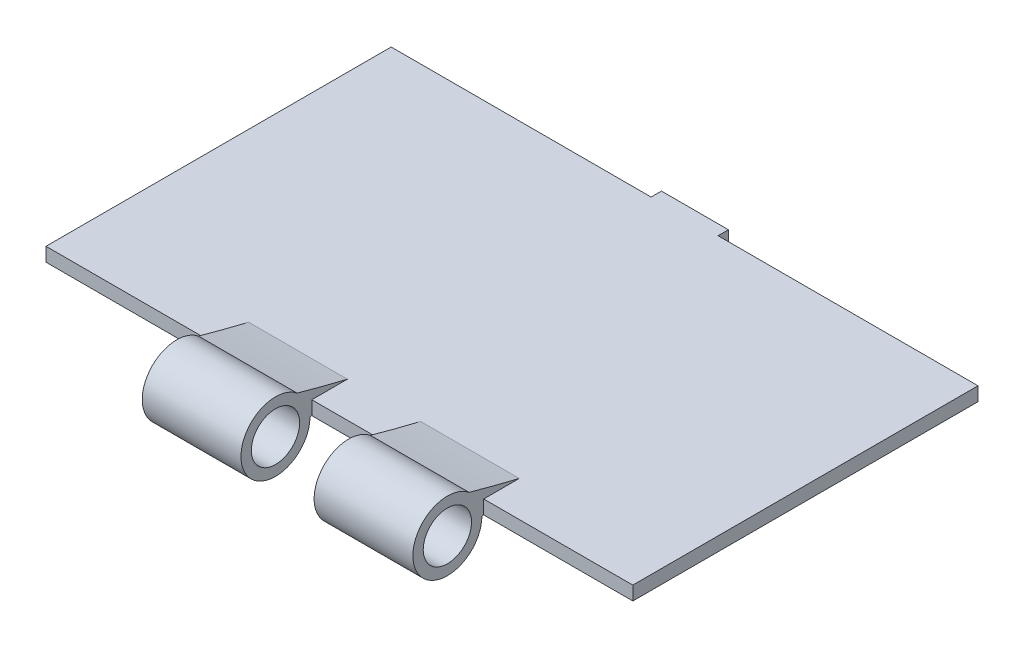
SolidWorks part; units mm, degrees
ref_plane "Plan de face" through (0, 0, 0) normal (0, 0, 1) x (1, 0, 0)
ref_plane "Plan de dessus" through (0, 0, 0) normal (0, 1, 0) x (1, 0, 0)
ref_plane "Plan de droite" through (0, 0, 0) normal (1, 0, 0) x (0, 0, -1)
sketch "Esquisse1" plane through (0, 0, 0) normal (0, 1, 0) x (1, 0, 0)
  line L1 (-42.5, 25) -> (42.5, 25)
  line L2 (-42.5, 25) -> (-42.5, -25)
  line L3 (-42.5, -25) -> (42.5, -25)
  line L4 (42.5, 25) -> (42.5, -25)
  line L5 (-42.5, 25) -> (42.5, -25) construction
  line L6 (-42.5, -25) -> (42.5, 25) construction
  point P0 (0, 0)
  dimension "D1" = 85
  dimension "D2" = 50
extrude "Boss.-Extru.1" add sketch "Esquisse1" along normal blind 2
ref_plane "Plan1" through (-18.3, 0, 0) normal (-1, 0, 0) x (0, 0, 1)
sketch "Esquisse2" plane through (-18.3, 0, 0) normal (-1, 0, 0) x (0, 0, 1)
  line L0 (25, 2) -> (25, 0) construction
  line L1 (-25, 2) -> (25, 2) construction
  line L2 (19.8455, 2) -> (25.3553, -0.0963)
  line L3 (-25, 0) -> (25, 0) construction
  circle A0 centre (30.26, 0) radius 5
  spline S0 degree 2 poles (27.1249, 3.895) (23.5046, 2.8738) (19.8455, 2) knots 0 0 0 1 1 1
  dimension "D1" = 10
  dimension "D2" = 5.26
  dimension "D3" = 0
extrude "Boss.-Extru.2" add sketch "Esquisse2" against normal blind 14.3 contours A0 S0 | A0 S0 L2 region at (-18.3, 1.9197, 23.8256) region at (-18.3, 0, 30.26)
sketch "Esquisse3" plane through (-18.3, 0, 0) normal (-1, 0, 0) x (0, 0, 1)
  circle A0 centre (30.26, 0) radius 3.5
  circle A1 centre (30.26, 0) radius 5 construction
  dimension "D1" = 0
  dimension "D2" = 7
extrude "Enlèv. mat.-Extru.1" cut sketch "Esquisse3" against normal up to surface (14.3 mm away) up to face at (-4, 0.9543, 26.8921)
pattern_linear "Répétition linéaire2" count 2 spacing 24.9 along (1, 0, 0) of "Enlèv. mat.-Extru.1", "Boss.-Extru.2"
ref_plane "Plan2" through (0, 0, 0) normal (1, 0, 0) x (0, 0, -1)
sketch "Esquisse4" plane through (0, 0, 0) normal (1, 0, 0) x (0, 0, -1)
  line L1 (25, 2) -> (26.5, 2)
  line L2 (25, 2) -> (25, -8)
  line L3 (25, -8) -> (26.5, -8)
  line L4 (26.5, 2) -> (26.5, -8)
  arc A0 (25, -8) -> (25, -6.5) centre (25, -7.25) cw
  dimension "D4" = 0.75
  dimension "D1" = 1.5
  dimension "D2" = 10
  dimension "D3" = 1.5
extrude "Boss.-Extru.3" add sketch "Esquisse4" along normal blind 4.85 and the other way blind 4.85 contours A0 L2 | L3 L4 L1 L2 region at (0, -7.25, -24.6817)
